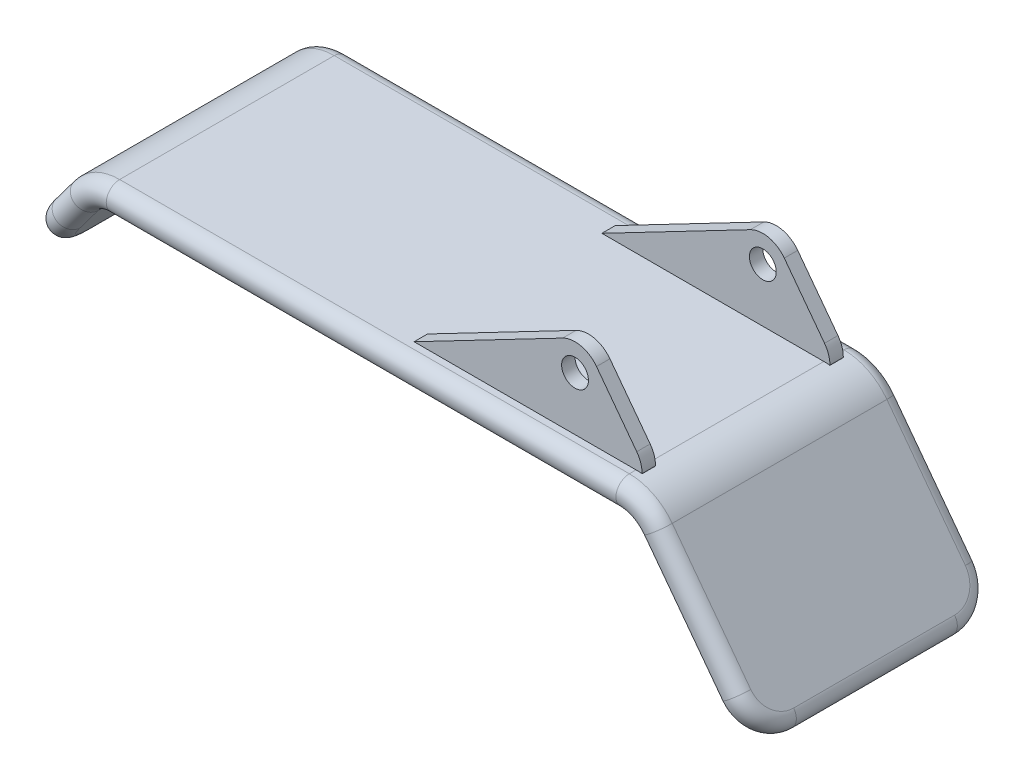
SolidWorks part; units mm, degrees
material "Plain Carbon Steel"
ref_plane "Front Plane" through (0, 0, 0) normal (0, 0, 1) x (1, 0, 0)
ref_plane "Top Plane" through (0, 0, 0) normal (0, 1, 0) x (1, 0, 0)
ref_plane "Right Plane" through (0, 0, 0) normal (1, 0, 0) x (0, 0, -1)
sketch "Sketch1" plane through (0, 0, 0) normal (0, 0, 1) x (1, 0, 0)
  line L0 (-19, 0) -> (19, 0)
  line L1 (20.6, -0.8) -> (28.25, -11)
  line L2 (-20.6, -0.8) -> (-23.75, -5)
  line L3 (0, 0) -> (0, -11) construction
  line L4 (-28.25, -11) -> (28.25, -11) construction
  line L5 (-23.75, -5) -> (-28.25, -11) construction
  arc A0 (-19, 0) -> (-20.6, -0.8) centre (-19, -2) ccw
  arc A1 (19, 0) -> (20.6, -0.8) centre (19, -2) cw
  point P10 (-20, 0)
  point P13 (20, 0)
  dimension "D5" = 2
  dimension "D1" = 11
  dimension "D2" = 52
  dimension "D3" = 40
  dimension "D4" = 5
extrude "Extrude-Thin1" add sketch "Sketch1" along normal mid plane 18 thin thin type one direction wall 2
fillet "Fillet1" radius 3 4 edges at (-24.55, -4.4, 9) (-24.55, -4.4, -9) (29.05, -10.4, -9) (29.05, -10.4, 9)
fillet "Fillet2" 2 edges at (0, 2, 9) (0, 0, 9) type full round first side face at (0, 2, 0) second side face at (0, 0, 0) middle face at (0.75, -1.3056, 9)
ref_plane "Plane1" through (0, 0, 7.5) normal (0, 0, 1) x (1, 0, 0)
sketch "Sketch2" plane through (0, 0, 7.5) normal (0, 0, 1) x (1, 0, 0)
  line L0 (2.45, 2) -> (13.5255, 7.7735)
  line L1 (-19, 2) -> (19, 2) construction
  line L2 (16.05, 7.2) -> (19.05, 3.2)
  line L3 (19.45, 2) -> (19.45, 1.9746)
  line L4 (2.45, 2) -> (19, 2)
  line L5 (19, 0) -> (-19, 0) construction
  arc A0 (13.5255, 7.7735) -> (16.05, 7.2) centre (14.45, 6) cw
  arc A1 (22.2, 0.4) -> (19, 2) centre (19, -2) ccw construction
  arc A2 (19.05, 3.2) -> (19.45, 2) centre (17.45, 2) cw
  arc A3 (19.45, 1.9746) -> (19, 2) centre (19, -2) ccw
  arc A4 (27.65, -10.2) -> (29.25, -9) centre (28.45, -9.6) ccw construction
  circle A5 centre (14.45, 6) radius 1
  dimension "D1" = 2
  dimension "D4" = 2
  dimension "D7" = 2
  dimension "D2" = 8
  dimension "D3" = 14
  dimension "D5" = 12
  dimension "D6" = 17
extrude "Extrude1" add sketch "Sketch2" against normal blind 1
mirror "Mirror1" about plane through (0, 0, 0) normal (0, 0, 1) of "Extrude1"
